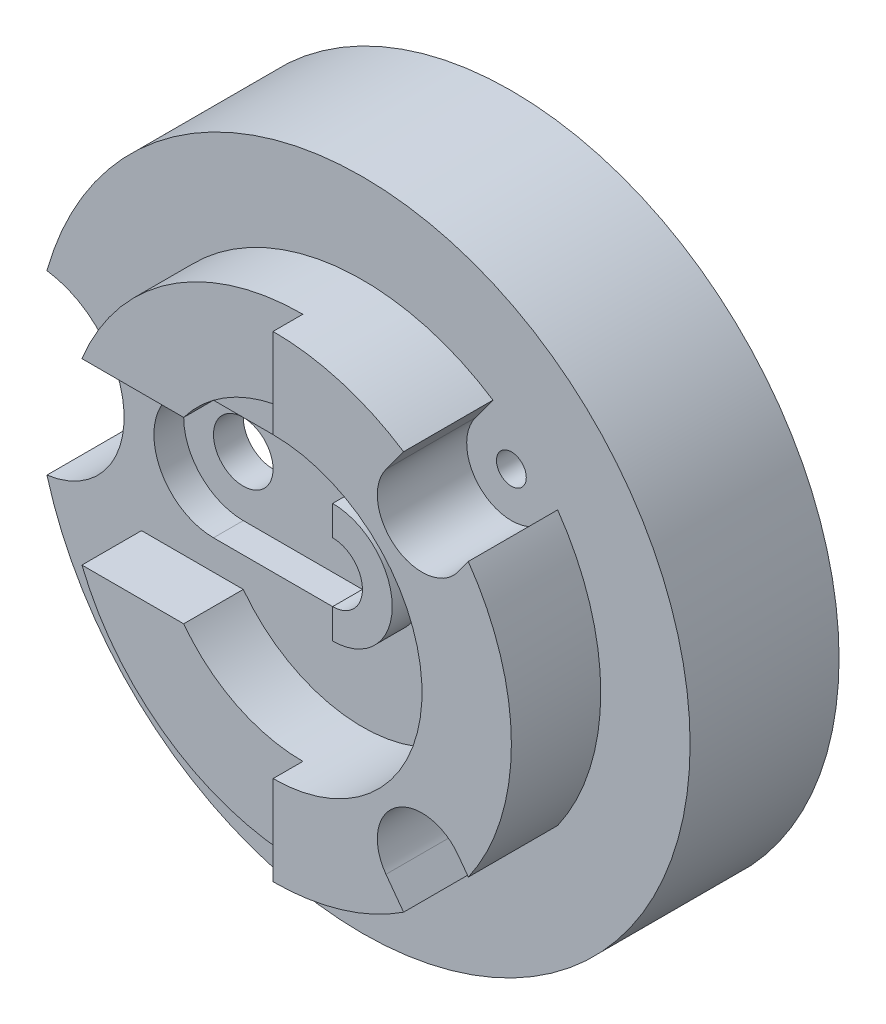
SolidWorks part; units mm, degrees
ref_plane "Front Plane" through (0, 0, 0) normal (0, 0, 1) x (1, 0, 0)
ref_plane "Top Plane" through (0, 0, 0) normal (0, 1, 0) x (1, 0, 0)
ref_plane "Right Plane" through (0, 0, 0) normal (1, 0, 0) x (0, 0, -1)
sketch "Sketch1" plane through (0, 0, 0) normal (0, 0, 1) x (1, 0, 0)
  circle A0 centre (0, 0) radius 110
  dimension "D1" = 220
extrude "Boss-Extrude2" add sketch "Sketch1" along normal blind 50
sketch "Sketch3" plane through (0, 0, 0) normal (0, 0, -1) x (-1, 0, 0)
  circle A0 centre (0, 0) radius 100
  dimension "D1" = 200
extrude "Cut-Extrude1" cut sketch "Sketch3" against normal blind 30
sketch "Sketch4" plane through (0, 0, 50) normal (0, 0, 1) x (1, 0, 0)
  circle A0 centre (0, 0) radius 10
  circle A1 centre (-50, 0) radius 10
  circle A2 centre (35, 0) radius 5
  dimension "D1" = 20
  dimension "D2" = 20
  dimension "D3" = 10
  dimension "D4" = 50
  dimension "D5" = 35
extrude "Cut-Extrude2" cut sketch "Sketch4" against normal blind 20
sketch "Sketch5" plane through (0, 0, 50) normal (0, 0, 1) x (1, 0, 0)
  line L0 (-50, 20) -> (0, 20)
  line L1 (-50, -20) -> (0, -20)
  line L2 (0, 10) -> (0, 20)
  arc A0 (0, 20) -> (0, -20) centre (0, 0) cw
  arc A1 (-50, 20) -> (-50, -20) centre (-50, 0) ccw
  circle A2 centre (0, 0) radius 10 construction
  circle M2 centre (-50, 0) radius 10
  circle M3 centre (0, 0) radius 10
  dimension "D1" = 20
  dimension "D2" = 20
  dimension "D3" = 50
  dimension "D4" = 50
extrude "Cut-Extrude3" cut sketch "Sketch5" against normal blind 10 contours L0 A1 L1 A0 M3 M2 region at (-25, 0, 50)
sketch "Sketch6" plane through (0, 0, 40) normal (0, 0, 1) x (1, 0, 0)
  line L0 (0, -20) -> (0, -10)
  line L1 (0, 10) -> (0, 20)
  line L2 (0, 10) -> (0, 20)
  circle A0 centre (0, 0) radius 10 construction
  arc A1 (0, -20) -> (0, 20) centre (0, 0) ccw construction
  arc A2 (0, 20) -> (0, -20) centre (0, 0) cw
  arc A3 (0, 10) -> (0, -10) centre (0, 0) cw
  arc M1 (0, -20) -> (0, 20) centre (0, 0) ccw
  circle M6 centre (0, 0) radius 10
extrude "Boss-Extrude3" add sketch "Sketch6" along normal blind 20 contours L1 L0 M6 M1 region at (0.4472, -15, 40)
sketch "Sketch7" plane through (0, 0, 50) normal (0, 0, 1) x (1, 0, 0)
  arc A0 (-105.9091, 29.7198) -> (-105.9091, -29.7198) centre (-110, 0) cw
  circle A1 centre (0, 0) radius 110 construction
  arc A2 (-105.9091, 29.7198) -> (-105.9091, -29.7198) centre (0, 0) ccw
  circle M2 centre (0, 0) radius 110
  dimension "D1" = 30
extrude "Cut-Extrude6" cut sketch "Sketch7" against normal blind 30 contours A0 M2 region at (-96.5596, 0, 50)
sketch "Sketch8" plane through (0, 0, 50) normal (0, 0, 1) x (1, 0, 0)
  line L0 (0, 50) -> (0, 80)
  line L1 (-74.162, 30) -> (-40, 30)
  arc A0 (0, 50) -> (-40, 30) centre (0, 0) ccw
  arc A1 (0, 80) -> (-74.162, 30) centre (0, 0) ccw
  dimension "D1" = 20
  dimension "D2" = 30
  dimension "D3" = 50
  dimension "D4" = 20
extrude "Boss-Extrude4" add sketch "Sketch8" along normal blind 20
sketch "Sketch9" plane through (0, 0, 50) normal (0, 0, 1) x (1, 0, 0)
  line L0 (0, -50) -> (0, -80)
  line L1 (-40, -30) -> (-74.162, -30)
  arc A0 (0, -50) -> (-40, -30) centre (0, 0) cw
  arc A1 (0, -80) -> (-74.162, -30) centre (0, 0) cw
  dimension "D1" = 30
  dimension "D2" = 20
  dimension "D3" = 20
  dimension "D4" = 50
extrude "Boss-Extrude5" add sketch "Sketch9" along normal blind 20
sketch "Sketch10" plane through (0, 0, 50) normal (0, 0, 1) x (1, 0, 0)
  line L0 (0, -80) -> (0, -50) construction
  line L1 (0, 80) -> (0, 50)
  line L2 (0, -50) -> (0, -80)
  arc A0 (0, 80) -> (0, -80) centre (0, 0) cw
  arc A1 (0, 50) -> (0, -50) centre (0, 0) cw
extrude "Boss-Extrude6" add sketch "Sketch10" along normal blind 30
sketch "Sketch11" plane through (0, 0, 80) normal (0, 0, 1) x (1, 0, 0)
  line L0 (37.9031, 58.8694) -> (43.816, 66.934)
  line L1 (61.3923, 40.2421) -> (65.5313, 45.8873)
  line L2 (62.0969, -41.1306) -> (65.5573, -45.8502)
  line L3 (37.9031, -58.8694) -> (43.816, -66.934)
  circle A0 centre (50, -50) radius 5
  circle A1 centre (50, 50) radius 5
  arc A2 (37.9031, 58.8694) -> (61.3923, 40.2421) centre (50, 50) ccw
  arc A3 (0, -80) -> (0, 80) centre (0, 0) ccw construction
  arc A4 (62.0969, -41.1306) -> (37.9031, -58.8694) centre (50, -50) ccw
  arc M1 (0, -80) -> (0, 80) centre (0, 0) ccw
  dimension "D1" = 10
  dimension "D2" = 10
  dimension "D7" = 15
  dimension "D10" = 15
  dimension "D3" = 50
  dimension "D4" = 50
  dimension "D5" = 50
  dimension "D6" = 50
  dimension "D8" = 10
  dimension "D9" = 7
  dimension "D11" = 10
extrude "Cut-Extrude8" cut sketch "Sketch11" against normal blind 30 contours L2 A4 L3 A0 M1 | L0 A2 L1 A1 M1 region at (55.3858, -57.113, 80) region at (41.2159, 62.6404, 80)
sketch "Sketch12" plane through (0, 0, 80) normal (0, 0, 1) x (1, 0, 0)
  circle A0 centre (50, 50) radius 5
  dimension "D1" = 10
extrude "Cut-Extrude9" cut sketch "Sketch12" against normal blind 50
sketch "Sketch13" plane through (0, 0, 80) normal (0, 0, 1) x (1, 0, 0)
  circle A0 centre (50, -50) radius 5
  dimension "D1" = 10
extrude "Cut-Extrude10" cut sketch "Sketch13" against normal blind 50
